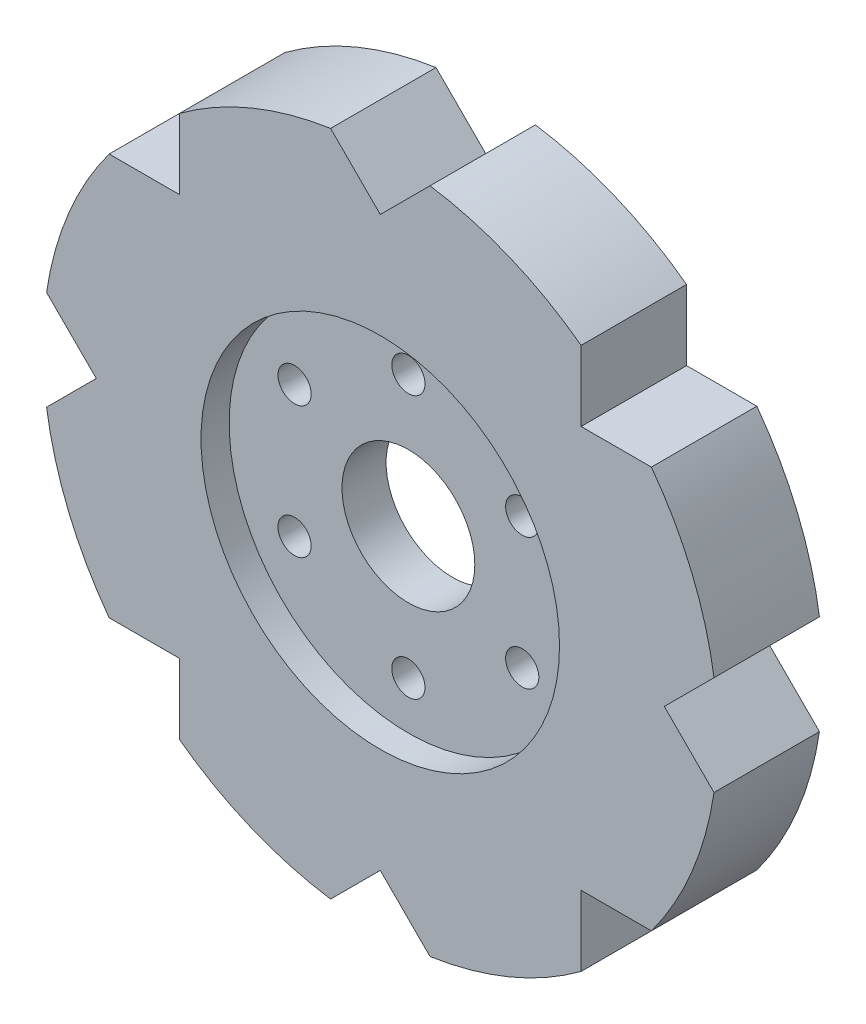
SolidWorks part; units mm, degrees
material "PE High Density Film"
ref_plane "Front Plane" through (0, 0, 0) normal (0, 0, 1) x (1, 0, 0)
ref_plane "Top Plane" through (0, 0, 0) normal (0, 1, 0) x (1, 0, 0)
ref_plane "Right Plane" through (0, 0, 0) normal (1, 0, 0) x (0, 0, -1)
sketch "Sketch1" plane through (0, 0, 0) normal (0, 0, 1) x (1, 0, 0)
  line L0 (0, 0) -> (0, 60.96) construction
  line L1 (-8.9803, 60.2949) -> (0, 51.3147)
  line L2 (0, 51.3147) -> (8.9803, 60.2949)
  line L3 (36.2849, 48.9849) -> (36.2849, 36.2849)
  line L4 (36.2849, 36.2849) -> (48.9849, 36.2849)
  line L5 (60.2949, 8.9803) -> (51.3147, 0)
  line L6 (51.3147, 0) -> (60.2949, -8.9803)
  line L7 (48.9849, -36.2849) -> (36.2849, -36.2849)
  line L8 (36.2849, -36.2849) -> (36.2849, -48.9849)
  line L9 (8.9803, -60.2949) -> (0, -51.3147)
  line L10 (0, -51.3147) -> (-8.9803, -60.2949)
  line L11 (-36.2849, -48.9849) -> (-36.2849, -36.2849)
  line L12 (-36.2849, -36.2849) -> (-48.9849, -36.2849)
  line L13 (-60.2949, -8.9803) -> (-51.3147, 0)
  line L14 (-51.3147, 0) -> (-60.2949, 8.9803)
  line L15 (-48.9849, 36.2849) -> (-36.2849, 36.2849)
  line L16 (-36.2849, 36.2849) -> (-36.2849, 48.9849)
  arc A0 (-60.2949, -8.9803) -> (-48.9849, -36.2849) centre (0, 0) ccw
  arc A1 (-48.9849, 36.2849) -> (-60.2949, 8.9803) centre (0, 0) ccw
  arc A2 (-36.2849, -48.9849) -> (-8.9803, -60.2949) centre (0, 0) ccw
  arc A3 (8.9803, -60.2949) -> (36.2849, -48.9849) centre (0, 0) ccw
  arc A4 (48.9849, -36.2849) -> (60.2949, -8.9803) centre (0, 0) ccw
  arc A5 (60.2949, 8.9803) -> (48.9849, 36.2849) centre (0, 0) ccw
  arc A6 (36.2849, 48.9849) -> (8.9803, 60.2949) centre (0, 0) ccw
  arc A7 (-8.9803, 60.2949) -> (-36.2849, 48.9849) centre (0, 0) ccw
  point P30 (0, 0)
  dimension "D1" = 121.92
  dimension "D2" = 45
  dimension "D3" = 12.7
  dimension "D4" = 8
extrude "Boss-Extrude1" add sketch "Sketch1" along normal blind 19.05
sketch "Sketch2" plane through (0, 0, 19.05) normal (0, 0, 1) x (1, 0, 0)
  circle A0 centre (0, 0) radius 12
  dimension "D1" = 24
extrude "Cut-Extrude1" cut sketch "Sketch2" against normal through all contours A0 region at (0, 0, 19.05)
sketch "Sketch3" plane through (0, 0, 19.05) normal (0, 0, 1) x (1, 0, 0)
  circle A0 centre (0, 0) radius 32.385
  dimension "D1" = 64.77
extrude "Cut-Extrude2" cut sketch "Sketch3" against normal blind 5.08
sketch "Sketch4" plane through (0, 0, 0) normal (0, 0, -1) x (-1, 0, 0)
  circle A0 centre (0, 0) radius 28.4
  dimension "D1" = 56.8
extrude "Cut-Extrude3" cut sketch "Sketch4" against normal blind 6
sketch "Sketch5" plane through (0, 0, 6) normal (0, 0, -1) x (-1, 0, 0)
  line L0 (0, 0) -> (0, 23.75) construction
  circle A0 centre (0, 0) radius 23.75 construction
  circle A1 centre (0, 23.75) radius 2.6
  circle A2 centre (20.5681, 11.875) radius 2.6
  circle A3 centre (20.5681, -11.875) radius 2.6
  circle A4 centre (0, -23.75) radius 2.6
  circle A5 centre (-20.5681, -11.875) radius 2.6
  circle A6 centre (-20.5681, 11.875) radius 2.6
  point P17 (0, 0)
  dimension "D1" = 47.5
  dimension "D2" = 5.2
  dimension "D3" = 6
hole_wizard "Ø6.0mm Dowel Hole1" positions "Sketch6" profile "Sketch8" hole size "Ø6.0" standard "ANSI Metric" end condition through all
sketch "Sketch6" plane through (0, 0, 6) normal (0, 0, -1) x (-1, 0, 0)
  point P0 (0, 23.75)
  point P3 (20.5681, 11.875)
  point P6 (20.5681, -11.875)
  point P9 (0, -23.75)
  point P13 (-20.5681, 11.875)
  point P16 (-20.5681, -11.875)
sketch "Sketch8" plane through (0, 23.75, 6) normal (1, 0, 0) x (0, 1, 0)
  line L0 (0, 0) -> (0, 13.05)
  line L1 (0, 13.05) -> (3, 13.05)
  line L2 (3, 13.05) -> (3, 0)
  line L5 (3, 0) -> (0, 0)
  line L11 (0, -6.35) -> (0, 107.95) construction
  dimension "Thru Hole Dia." = 6
  dimension "Thru Hole Depth" = 13.05
